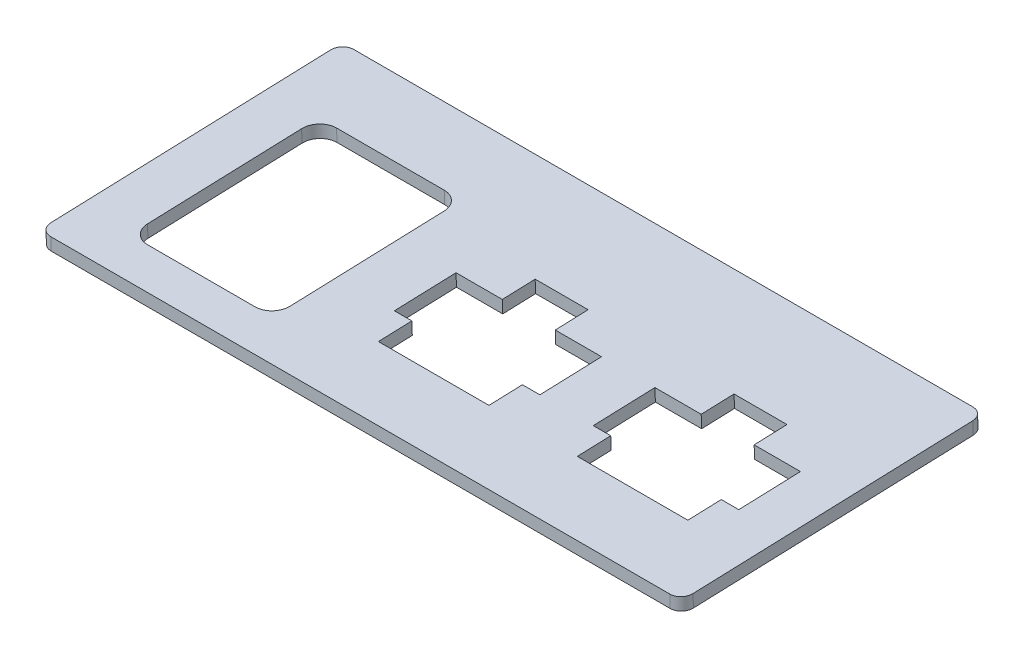
SolidWorks part; units mm, degrees
ref_plane "Front Plane" through (0, 0, 0) normal (0, 0, 1) x (1, 0, 0)
ref_plane "Top Plane" through (0, 0, 0) normal (0, 1, 0) x (1, 0, 0)
ref_plane "Right Plane" through (0, 0, 0) normal (1, 0, 0) x (0, 0, -1)
sketch "Sketch1" plane through (0, -71.9872, -2.5138) normal (0, 0.9994, 0.0349) x (1, 0, 0)
  line L0 (-56.175, 48.6398) -> (56.175, 48.6398) construction
  line L1 (-52.175, -2.9116) -> (-56.175, -2.9116) construction
  line L8 (-55.175, -4.2116) -> (55.175, -4.2116)
  line L9 (55.175, -4.2116) -> (55.175, 47.8898)
  line L10 (55.175, 47.8898) -> (-55.175, 47.8898)
  line L11 (-55.175, 47.8898) -> (-55.175, -4.2116)
  dimension "D4" = 0.75
  dimension "D1" = 1.3
  dimension "D2" = 3.0034
  dimension "D3" = 3.0034
extrude "Boss-Extrude1" add sketch "Sketch1" along normal blind 2.2
sketch "Sketch2" plane through (0, -71.9872, -2.5138) normal (0, -0.9994, -0.0349) x (1, 0, 0)
  line L0 (-4.05, -24.2621) -> (-4.05, -29.9121)
  line L1 (-43.425, -2.6621) -> (-24.925, -2.6621)
  line L2 (-46.425, -5.6621) -> (-46.425, -32.1621)
  line L3 (-43.425, -35.1621) -> (-24.925, -35.1621)
  line L4 (-21.925, -5.6621) -> (-21.925, -32.1621)
  line L5 (-12, -13.6621) -> (-9, -13.6621)
  line L6 (-12, -13.6621) -> (-12, -24.2621)
  line L7 (-12, -24.2621) -> (-4.05, -24.2621)
  line L8 (13, -13.6621) -> (13, -24.2621)
  line L9 (-9, -7.9121) -> (10, -7.9121)
  line L10 (-9, -7.9121) -> (-9, -13.6621)
  line L11 (-4.05, -29.9121) -> (5.05, -29.9121)
  line L12 (10, -7.9121) -> (10, -13.6621)
  line L13 (10, -13.6621) -> (13, -13.6621)
  line L14 (5.05, -24.2621) -> (5.05, -29.9121)
  line L15 (5.05, -24.2621) -> (13, -24.2621)
  line L16 (-13, -5.4121) -> (14, -32.4121) construction
  line L17 (-13, -5.4121) -> (14, -5.4121) construction
  line L18 (-13, -5.4121) -> (-13, -32.4121) construction
  line L19 (-13, -32.4121) -> (14, -32.4121) construction
  line L20 (14, -5.4121) -> (14, -32.4121) construction
  line L21 (17.5875, 3.7502) -> (17.5875, -36.664) construction
  line L22 (47.175, -18.9621) -> (22.175, -18.9621) construction
  line L23 (34.675, -7.9121) -> (34.675, -29.9121) construction
  line L24 (21.175, -5.4121) -> (21.175, -32.4121) construction
  line L25 (48.175, -32.4121) -> (21.175, -32.4121) construction
  line L26 (48.175, -5.4121) -> (48.175, -32.4121) construction
  line L27 (48.175, -5.4121) -> (21.175, -5.4121) construction
  line L28 (-48.175, -18.9121) -> (-46.425, -18.9121) construction
  line L29 (-48.175, -0.9121) -> (-20.175, -0.9121) construction
  line L30 (-48.175, -0.9121) -> (-48.175, -36.9121) construction
  line L31 (-48.175, -36.9121) -> (-20.175, -36.9121) construction
  line L32 (-20.175, -0.9121) -> (-20.175, -36.9121) construction
  line L33 (-34.175, -2.6621) -> (-34.175, -0.9121) construction
  line L34 (0.5, -7.9121) -> (0.5, -29.9121) construction
  line L35 (-12, -18.9621) -> (13, -18.9621) construction
  line L36 (48.175, -5.4121) -> (21.175, -32.4121) construction
  line L37 (30.125, -24.2621) -> (22.175, -24.2621)
  line L38 (30.125, -24.2621) -> (30.125, -29.9121)
  line L39 (25.175, -13.6621) -> (22.175, -13.6621)
  line L40 (25.175, -7.9121) -> (25.175, -13.6621)
  line L41 (39.225, -29.9121) -> (30.125, -29.9121)
  line L42 (44.175, -7.9121) -> (44.175, -13.6621)
  line L43 (44.175, -7.9121) -> (25.175, -7.9121)
  line L44 (22.175, -13.6621) -> (22.175, -24.2621)
  line L45 (47.175, -24.2621) -> (39.225, -24.2621)
  line L46 (47.175, -13.6621) -> (47.175, -24.2621)
  line L47 (47.175, -13.6621) -> (44.175, -13.6621)
  line L48 (39.225, -24.2621) -> (39.225, -29.9121)
  line L49 (21.175, -18.9121) -> (14, -18.9121) construction
  line L51 (48.175, -18.9121) -> (52.175, -18.9121) construction
  line L52 (55.175, 4.2116) -> (55.175, -47.8898) construction
  line L53 (-46.7914, -40.6398) -> (46.7914, -40.6398) construction
  line L54 (-13, -18.9121) -> (-20.175, -18.9121) construction
  line L55 (-34.175, -0.9121) -> (-34.175, 2.8156) construction
  line L56 (-34.175, -36.9121) -> (-34.175, -40.6398) construction
  line L57 (-55.175, -47.8898) -> (-55.175, 4.2116) construction
  line L58 (-48.175, -18.9121) -> (-52.175, -18.9121) construction
  line L59 (-53.075, 2.8156) -> (53.075, 2.8156) construction
  arc A0 (-46.425, -32.1621) -> (-43.425, -35.1621) centre (-43.425, -32.1621) ccw
  arc A1 (-24.925, -35.1621) -> (-21.925, -32.1621) centre (-24.925, -32.1621) ccw
  arc A2 (-24.925, -2.6621) -> (-21.925, -5.6621) centre (-24.925, -5.6621) cw
  arc A3 (-43.425, -2.6621) -> (-46.425, -5.6621) centre (-43.425, -5.6621) ccw
  point P28 (0.5, -18.9121)
  point P63 (34.675, -18.9121)
  dimension "D1" = 3
  dimension "D2" = 32.5
  dimension "D3" = 24.5
  dimension "D4" = 28
  dimension "D5" = 36
  dimension "D6" = 25
  dimension "D7" = 22
  dimension "D8" = 10.6
  dimension "D9" = 19
  dimension "D10" = 9.1
  dimension "D11" = 5.75
  dimension "D12" = 27
  dimension "D13" = 27
  dimension "D14" = 4
  dimension "D15" = 3
  dimension "D16" = 3
extrude "Cut-Extrude1" cut sketch "Sketch2" against normal up to next
fillet "Fillet1" radius 2 4 edges at (-55.175, -71.0348, 1.7336) (55.175, -71.0348, 1.7336) (55.175, -69.2165, -50.336) (-55.175, -69.2165, -50.336)
